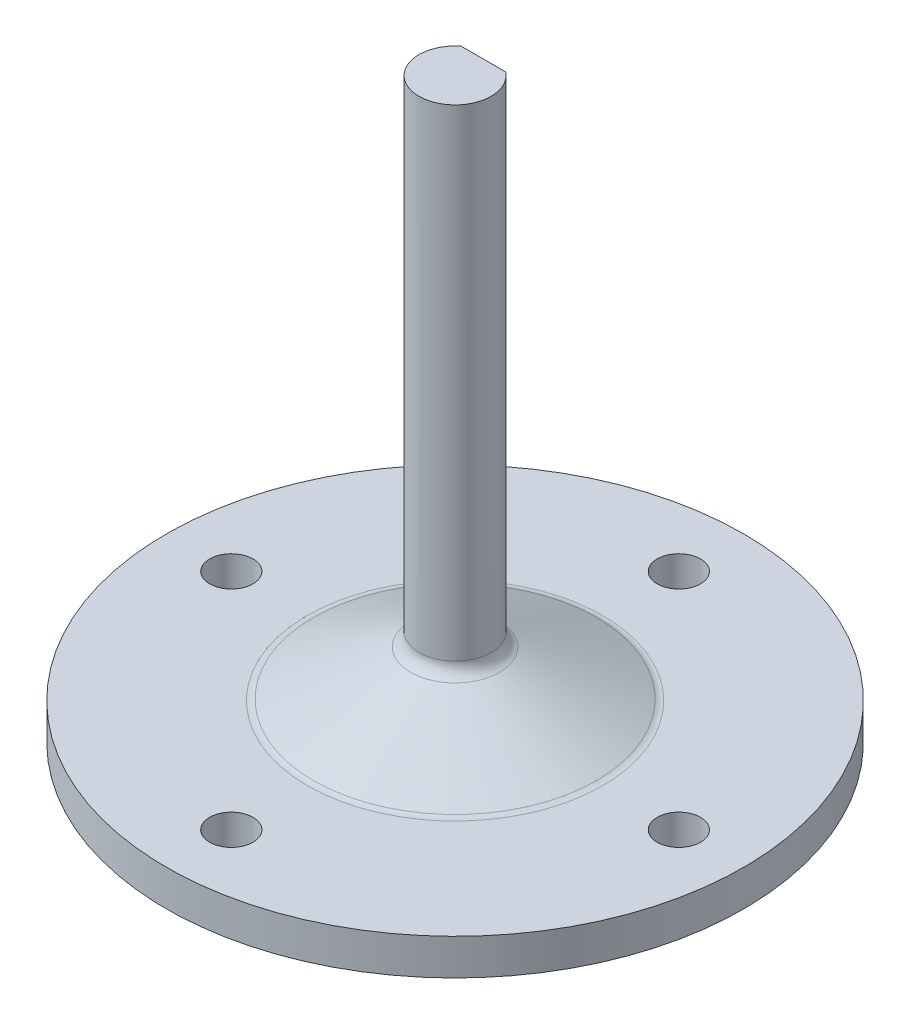
SolidWorks part; units mm, degrees
ref_plane "Front Plane" through (0, 0, 0) normal (0, 0, 1) x (1, 0, 0)
ref_plane "Top Plane" through (0, 0, 0) normal (0, 1, 0) x (1, 0, 0)
ref_plane "Right Plane" through (0, 0, 0) normal (1, 0, 0) x (0, 0, -1)
sketch "Sketch1" plane through (0, 0, 0) normal (0, 1, 0) x (1, 0, 0)
  circle A0 centre (0, 0) radius 20
  circle A1 centre (0, 15.5) radius 1.5
  circle A2 centre (15.5, 0) radius 1.5
  circle A3 centre (0, -15.5) radius 1.5
  circle A4 centre (-15.5, 0) radius 1.5
  point P5 (-19.8847, 6.538)
  point P6 (0, 0)
  point P14 (0, 0)
  dimension "D1" = 40
  dimension "D2" = 3
  dimension "D3" = 15.5
  dimension "D4" = 4
sketch "Sketch2" plane through (0, 0, 0) normal (1, 0, 0) x (0, 0, -1)
  line L0 (0, 0) -> (0, 68.0549)
  line L1 (1.5, 0) -> (-1.5, 0) construction
  line L2 (-20, 0) -> (-20, 2.5)
  line L3 (20, 0) -> (-20, 0) construction
  line L4 (-20, 2.5) -> (-10, 2.5)
  line L5 (-10, 2.5) -> (-2.5, 6)
  line L6 (-2.5, 6) -> (-2.5, 40)
  line L7 (-2.5, 40) -> (0, 40)
  line L8 (20, 0) -> (-20, 0)
  point P7 (-2.5, 7)
  point P8 (0, 0)
  point P13 (0, 0)
  point P15 (-27.5, 2.2234)
  dimension "D1" = 2.5
  dimension "D2" = 10
  dimension "D3" = 6
  dimension "D4" = 40
  dimension "D5" = 2.5
revolve "Revolve1" add sketch "Sketch2" angle 360 about L0 region at (0, 0.4472, 10)
fillet "Fillet1" radius 1 2 edges at (0, 2.5, -10) (0, 6, -2.5)
extrude "Cut-Extrude1" cut sketch "Sketch1" along normal up to surface (2.5 mm away) contours A3 | A4 | A1 | A2 region at (0, 0, -15.5) region at (15.5, 0, 0) region at (0, 0, 15.5) region at (-15.5, 0, 0) up to face at (0, 2.5, 10.2218)
sketch "Sketch3" plane through (0, 40, 0) normal (0, 1, 0) x (1, 0, 0)
  line L0 (-1.5425, 1.9674) -> (1.5425, 1.9674)
  circle A0 centre (0, 0) radius 2.5 construction
  circle A1 centre (0, 0) radius 2.5
  circle M2 centre (0, 0) radius 2.5
  dimension "D1" = 3.085
extrude "Cut-Extrude2" cut sketch "Sketch3" against normal blind 33.2 contours L0 M2 region at (0, 40, -2.1825)
